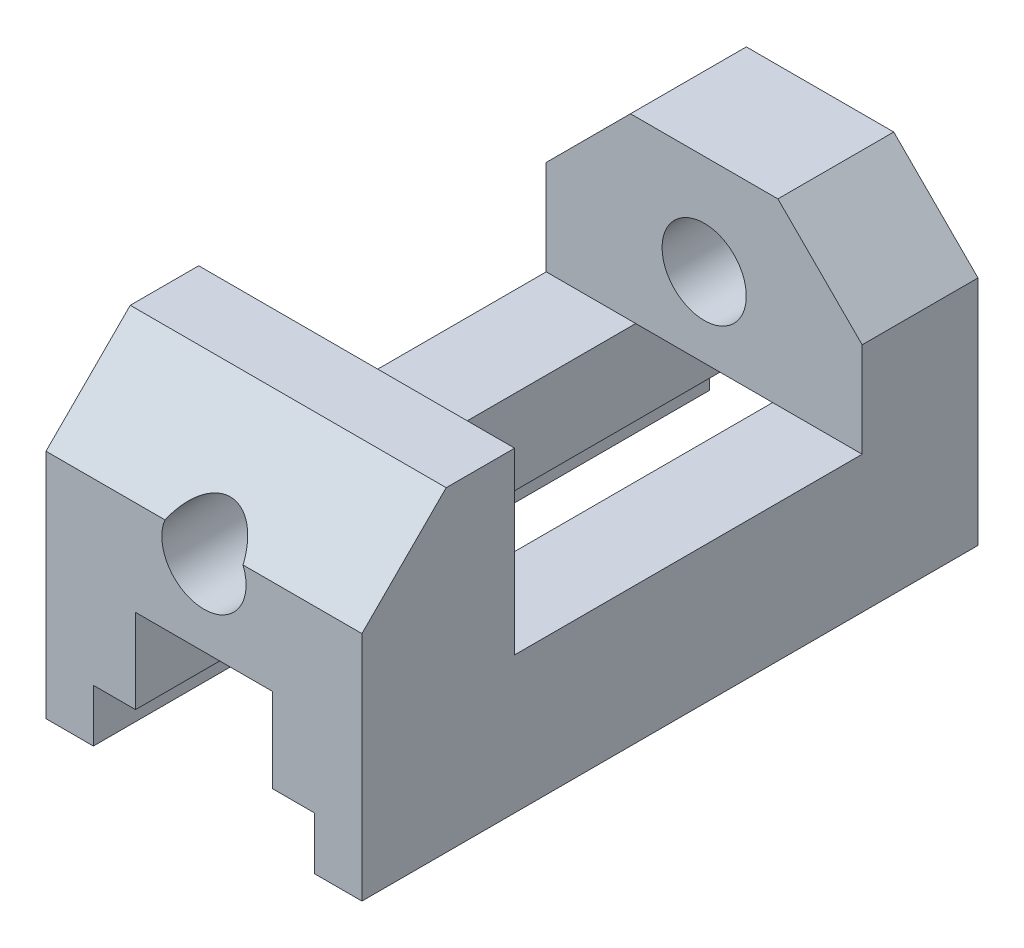
SolidWorks part; units mm, degrees
ref_plane "Front Plane" through (0, 0, 0) normal (0, 0, 1) x (1, 0, 0)
ref_plane "Top Plane" through (0, 0, 0) normal (0, 1, 0) x (1, 0, 0)
ref_plane "Right Plane" through (0, 0, 0) normal (1, 0, 0) x (0, 0, -1)
sketch "Sketch1" plane through (0, 0, 0) normal (0, 0, 1) x (1, 0, 0)
  line L0 (30, 19) -> (-30, 19)
  line L1 (0, -44.4768) -> (0, 44.4768) construction
  line L2 (30, 19) -> (30, -41)
  line L3 (30, -41) -> (21, -41)
  line L4 (21, -41) -> (21, -31)
  line L5 (21, -31) -> (13, -31)
  line L6 (13, -31) -> (13, -15)
  line L7 (-30, 19) -> (-30, -41)
  line L8 (-30, -41) -> (-21, -41)
  line L9 (-21, -41) -> (-21, -31)
  line L10 (-21, -31) -> (-13, -31)
  line L11 (-13, -31) -> (-13, -15)
  line L12 (13, -15) -> (-13, -15)
  line L13 (14, 19) -> (30, 3)
  line L14 (-14, 19) -> (-30, 3)
  circle A0 centre (0, 0) radius 8
  point P8 (0, 0)
  dimension "D1" = 16
  dimension "D2" = 60
  dimension "D3" = 60
  dimension "D4" = 10
  dimension "D5" = 8
  dimension "D6" = 16
  dimension "D7" = 41
  dimension "D8" = 26
  dimension "D9" = 16
  dimension "D10" = 45
extrude "Boss-Extrude1" add sketch "Sketch1" along normal blind 117 contours L1 L12 L6 L5 L4 L3 L2 L13 L0 A0 | L12 L1 A0 L0 L14 L7 L8 L9 L10 L11 | L0 L13 L2 | L14 L0 L7 region at (24.6667, 13.6667, 0) region at (17.2907, -7.9806, 0) region at (-17.2907, -7.9806, 0) region at (-24.6667, 13.6667, 0)
sketch "Sketch2" plane through (0, 0, 0) normal (1, 0, 0) x (0, 0, -1)
  line L0 (-117, 3) -> (-101, 19)
  line L1 (-117, 19) -> (-117, -41) construction
  line L2 (-117, 19) -> (0, 19) construction
  line L3 (-117, 3) -> (-117, 19)
  line L4 (-117, 19) -> (-101, 19)
  line L5 (-88, 19) -> (-88, -15)
  line L6 (-88, -15) -> (-22, -15)
  line L7 (-22, -15) -> (-22, 19)
  line L8 (-22, 19) -> (-88, 19)
  line L9 (-117, -15) -> (0, -15) construction
  dimension "D1" = 16
  dimension "D2" = 45
  dimension "D3" = 29
  dimension "D4" = 22
extrude "Cut-Extrude1" cut sketch "Sketch2" against normal through all both and the other way through all
extrude "Cut-Extrude2" cut sketch "Sketch1<3>" along normal up to surface (22 mm away) contours L0 L13 L2 | L14 L0 L7 region at (24.6667, 13.6667, 0) region at (-24.6667, 13.6667, 0) up to face at (-8, 0, 22)
sketch "Sketch1<3>" plane through (0, 0, 0) normal (0, 0, 1) x (1, 0, 0) same geometry as "Sketch1"
